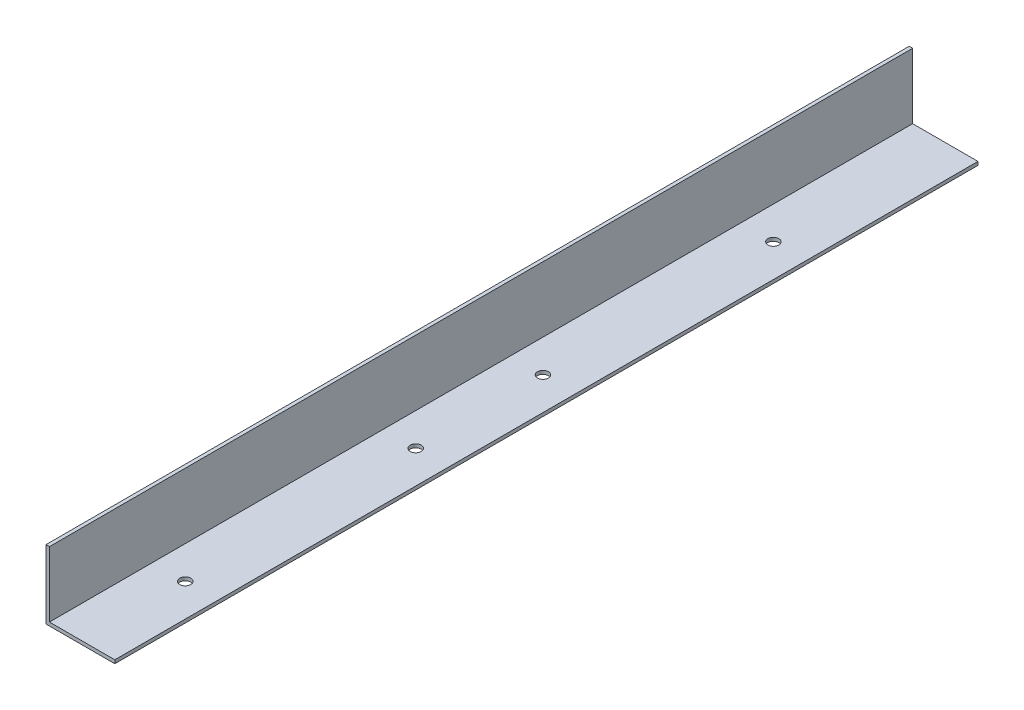
SolidWorks part; units mm, degrees
material "1060 Сплав"
ref_plane "Спереди" through (0, 0, 0) normal (0, 0, 1) x (1, 0, 0)
ref_plane "Сверху" through (0, 0, 0) normal (0, 1, 0) x (1, 0, 0)
ref_plane "Справа" through (0, 0, 0) normal (1, 0, 0) x (0, 0, -1)
sketch "Эскиз1" plane through (0, 0, 0) normal (0, 0, 1) x (1, 0, 0)
  line L0 (0, 0) -> (0, 20)
  line L1 (0, 20) -> (1, 20)
  line L2 (1, 20) -> (1, 1)
  line L3 (1, 1) -> (20, 1)
  line L4 (20, 1) -> (20, 0)
  line L5 (20, 0) -> (0, 0)
  dimension "D1" = 20
  dimension "D2" = 1
extrude "Бобышка-Вытянуть1" add sketch "Эскиз1" along normal blind 251
sketch "Эскиз2" plane through (0, 1, 0) normal (0, 1, 0) x (1, 0, 0)
  line L0 (10.5, 0) -> (10.5, -251) construction
  line L1 (20, 0) -> (1, 0) construction
  line L2 (20, -251) -> (1, -251) construction
  line L3 (20, -125.5) -> (10.5, -125.5) construction
  line L4 (20, -251) -> (20, 0) construction
  line L5 (10.5, -50) -> (10.5, -117) construction
  line L6 (20, -83.5) -> (10.5, -83.5) construction
  line L7 (1, -40) -> (20, -40) construction
  line L8 (1, -251) -> (1, 0) construction
  line L9 (1, -231) -> (20, -231) construction
  circle A0 centre (10.5, -50) radius 1.6
  circle A1 centre (10.5, -117) radius 1.6
  circle A2 centre (10.5, -221) radius 1.6
  circle A3 centre (10.5, -154) radius 1.6
  point P17 (10.5, -83.5)
  dimension "D1" = 3.2
  dimension "D2" = 3.2
  dimension "D3" = 67
  dimension "D6" = 10
  dimension "D8" = 3.2
  dimension "D10" = 67
  dimension "D4" = 125.5
  dimension "D5" = 40
  dimension "D7" = 20
  dimension "D9" = 10
extrude "Вырез-Вытянуть1" cut sketch "Эскиз2" against normal through all
